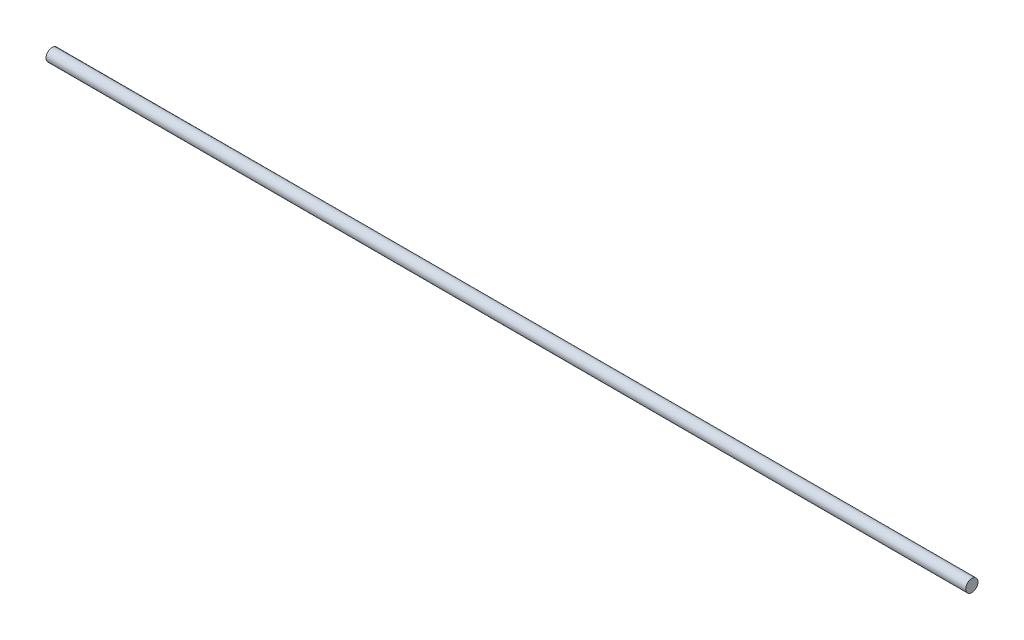
SolidWorks part; units mm, degrees
material "Alloy Steel (SS)"
ref_plane "Front Plane" through (0, 0, 0) normal (0, 0, 1) x (1, 0, 0)
ref_plane "Top Plane" through (0, 0, 0) normal (0, 1, 0) x (1, 0, 0)
ref_plane "Right Plane" through (0, 0, 0) normal (1, 0, 0) x (0, 0, -1)
sketch "Sketch1" plane through (0, 0, 0) normal (1, 0, 0) x (0, 0, -1)
  circle A0 centre (0, 0) radius 2
  dimension "D1" = 4
extrude "Boss-Extrude1" add sketch "Sketch1" along normal mid plane 299.974
